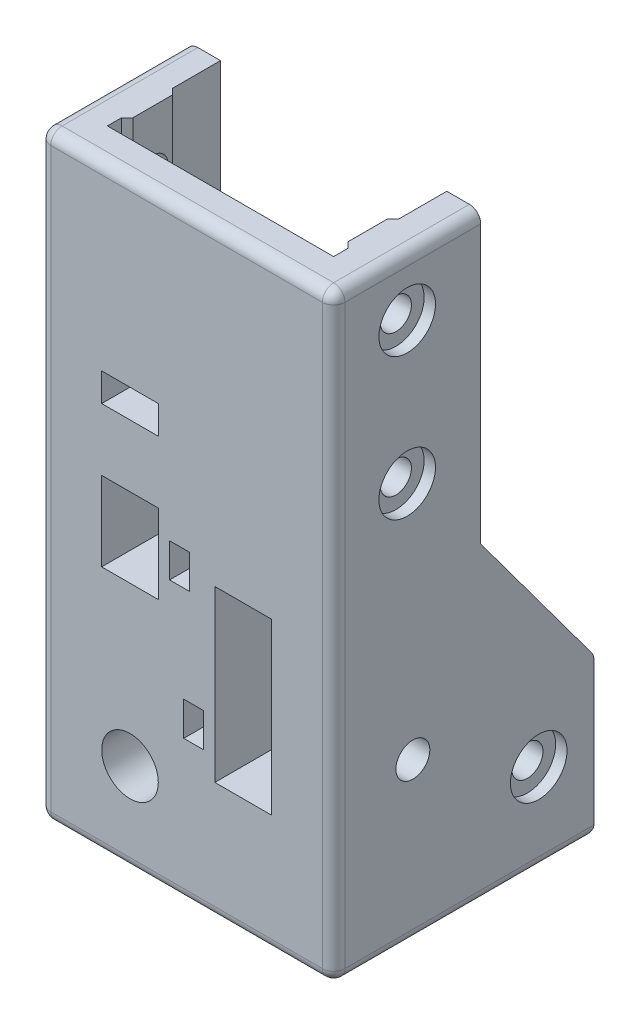
SolidWorks part; units mm, degrees
ref_plane "Front Plane" through (0, 0, 0) normal (0, 0, 1) x (1, 0, 0)
ref_plane "Top Plane" through (0, 0, 0) normal (0, 1, 0) x (1, 0, 0)
ref_plane "Right Plane" through (0, 0, 0) normal (1, 0, 0) x (0, 0, -1)
sketch "Sketch1" plane through (0, 0, 0) normal (1, 0, 0) x (0, 0, -1)
  line L0 (0, 106) -> (26, 106)
  line L1 (0, 0) -> (46, 0)
  line L2 (0, 106) -> (0, 0)
  line L3 (46, 0) -> (46, 55)
  line L4 (26, 106) -> (26, 55)
  line L5 (26, 55) -> (46, 55)
  line L6 (6, 106) -> (6, 58)
  line L7 (46, 6) -> (26, 6)
  line L8 (6, 58) -> (26, 58)
  line L10 (26, 55) -> (26, 6)
  circle A0 centre (13, 95.75) radius 2.75
  circle A1 centre (13, 95.75) radius 5
  circle A2 centre (13, 70.75) radius 2.75
  circle A3 centre (13, 70.75) radius 5
  circle A4 centre (36.25, 15.75) radius 2.75
  circle A5 centre (36.25, 15.75) radius 5
  point P9 (13, 106)
  point P15 (8.8717, 6)
  point P19 (26, 58)
  point P20 (35.1327, 30.1857)
  point P21 (26, 6)
  point P26 (35.8678, 13.2319)
  dimension "D6" = 2.75
  dimension "D7" = 5
  dimension "D1" = 46
  dimension "D2" = 26
  dimension "D3" = 106
  dimension "D4" = 55
  dimension "D5" = 10.25
  dimension "D8" = 25
  dimension "D9" = 6
  dimension "D10" = 6
  dimension "D11" = 58
  dimension "D12" = 15.75
  dimension "D13" = 9.75
extrude "Boss-Extrude1" add sketch "Sketch1" along normal mid plane 52 contours L10 L4 L8 L6 L0 L2 L1 L3 L7 | L5 L10 L7 L3 | A3 A2 | A1 A0 | L6 L8 L4 L0 A3 A1 | A5 A4 region at (0, 35.3382, -12.9374) region at (0, 81.7555, -16.5869) region at (0, 31.7851, -35.9782) region at (0, 95.75, -8.1414) region at (0, 70.75, -8.1414) region at (0, 15.75, -31.3914)
chamfer "Chamfer1" distance 27 distance2 20 1 edges at (0, 55, -46) first distance on face at (0, 27.5, -46)
extrude "Cut-Extrude1" cut sketch "Sketch1<3>" against normal mid plane 40 contours L5 L10 L7 L3 | L6 L8 L4 L0 A3 A1 | A3 A2 | A1 A0 | A5 A4 region at (0, 81.7555, -16.5869) region at (0, 31.7851, -35.9782) region at (0, 95.75, -8.1414) region at (0, 70.75, -8.1414) region at (0, 15.75, -31.3914)
sketch "Sketch1<3>" plane through (0, 0, 0) normal (1, 0, 0) x (0, 0, -1) same geometry as "Sketch1"
sketch "Sketch2" plane through (0, 0, -26) normal (0, 0, -1) x (-1, 0, 0)
  line L0 (20, 58) -> (-20, 58) construction
  line L1 (-20, 58) -> (-5, 58)
  line L2 (-20, 58) -> (-20, 46)
  line L3 (-20, 46) -> (-5, 46)
  line L4 (-5, 58) -> (-5, 46)
  line L5 (5, 58) -> (15, 58)
  line L6 (5, 58) -> (5, 44)
  line L7 (5, 44) -> (15, 44)
  line L8 (15, 58) -> (15, 44)
  dimension "D1" = 15
  dimension "D2" = 12
  dimension "D3" = 10
  dimension "D4" = 14
  dimension "D5" = 10
extrude "Cut-Extrude2" cut sketch "Sketch2" against normal up to surface (20 mm away) up to face at (0, 82, -6)
sketch "Sketch3" plane through (0, 0, 0) normal (0, 0, 1) x (1, 0, 0)
  line L0 (5, 51) -> (15, 51)
  line L1 (-15, 74) -> (-5, 74)
  line L2 (-15, 74) -> (-15, 44)
  line L3 (-15, 44) -> (-5, 44)
  line L4 (-5, 74) -> (-5, 44)
  line L5 (5, 51) -> (5, 21)
  line L6 (-5, 44) -> (-15, 44) construction
  line L7 (-15, 44) -> (-15, 58) construction
  line L8 (-15, 69) -> (-5, 69)
  line L9 (-15, 58) -> (-5, 58)
  line L10 (-20, 58) -> (-15, 58) construction
  line L11 (5, 21) -> (15, 21)
  line L12 (15, 51) -> (15, 21)
  line L13 (5, 46) -> (15, 46)
  line L14 (5, 35) -> (15, 35)
  line L15 (20, 46) -> (5, 46) construction
  line L16 (5, 46) -> (5, 58) construction
  line L17 (10, 21) -> (10, 35) construction
  line L18 (-10, 44) -> (-10, 58) construction
  line L19 (0.5, 48) -> (-3, 48)
  line L20 (3, 25) -> (-0.5, 25)
  line L21 (3, 25) -> (3, 31)
  line L22 (3, 31) -> (-0.5, 31)
  line L23 (-0.5, 25) -> (-0.5, 31)
  line L24 (3, 25) -> (-0.5, 31) construction
  line L25 (3, 31) -> (-0.5, 25) construction
  line L26 (0.5, 48) -> (0.5, 54)
  line L27 (0.5, 54) -> (-3, 54)
  line L28 (-3, 48) -> (-3, 54)
  line L29 (0.5, 48) -> (-3, 54) construction
  line L30 (0.5, 54) -> (-3, 48) construction
  circle A0 centre (-10, 16) radius 5
  circle A1 centre (-10, 16) radius 2.75
  point P23 (-10, 44)
  point P34 (1.25, 28)
  point P39 (0, 0)
  point P40 (10, 28)
  point P41 (-2.506, 28)
  point P42 (-1.25, 51)
  point P47 (-10, 51)
  dimension "D9" = 5
  dimension "D10" = 2.75
  dimension "D1" = 11
  dimension "D2" = 10
  dimension "D3" = 10
  dimension "D4" = 5
  dimension "D5" = 5
  dimension "D6" = 11
  dimension "D7" = 14
  dimension "D8" = 28
  dimension "D11" = 3.5
  dimension "D12" = 6
  dimension "D13" = 2
  dimension "D14" = 3.5
  dimension "D15" = 6
  dimension "D16" = 2
extrude "Cut-Extrude3" cut sketch "Sketch3" against normal through all contours A1 | L5 L13 L12 L0 | L14 L5 L11 L12 | L9 L2 L3 L4 | L2 L8 L4 L1 region at (10, 48.5, 0) region at (10, 28, 0) region at (-10, 71.5, 0) region at (-10, 51, 0) region at (-10, 16, 0)
extrude "Cut-Extrude4" cut sketch "Sketch3<3>" against normal blind 22 contours A0 A1 | L23 L20 L21 L22 | L28 L19 L26 L27 region at (-1.25, 51, 0) region at (1.25, 28, 0) region at (-14.8586, 16, 0)
sketch "Sketch3<3>" plane through (0, 0, 0) normal (0, 0, 1) x (1, 0, 0) same geometry as "Sketch3"
extrude "Cut-Extrude5" cut sketch "Sketch3<4>" against normal blind 11 contours L5 L14 L12 L13 region at (10, 40.5, 0)
sketch "Sketch3<4>" plane through (0, 0, 0) normal (0, 0, 1) x (1, 0, 0) same geometry as "Sketch3"
sketch "Sketch4" plane through (0, 0, 0) normal (1, 0, 0) x (0, 0, -1)
  line L0 (26, 21) -> (26, 35) construction
  line L2 (26, 44) -> (26, 58) construction
  line L3 (0, 106) -> (0, 0) construction
  circle A0 centre (14, 28) radius 1.5
  circle A1 centre (14, 28) radius 3
  circle A2 centre (14, 51) radius 1.5
  circle A3 centre (14, 51) radius 3
  point P3 (10.9426, 24.6286)
  point P6 (0, 0)
  point P7 (26, 28)
  point P8 (0, 0)
  point P15 (12.7722, 46.8378)
  point P16 (0, 0)
  point P17 (0, 0)
  point P20 (26, 51)
  point P21 (0, 0)
  point P22 (19.6179, 28)
  dimension "D1" = 6
  dimension "D2" = 3
  dimension "D3" = 14
extrude "Cut-Extrude6" cut sketch "Sketch4" against normal up to surface (15 mm away) and the other way through all contours A0 region at (0, 28, -14) up to face at (-15, 52.4, -11.6)
extrude "Cut-Extrude7" cut sketch "Sketch4<3>" against normal through all and the other way up to surface (15 mm away) contours A2 region at (0, 51, -14) other way up to face at (15, 26.5, -14)
sketch "Sketch4<3>" plane through (0, 0, 0) normal (1, 0, 0) x (0, 0, -1) same geometry as "Sketch4"
extrude "Cut-Extrude8" cut sketch "Sketch4<4>" against normal blind 8 from surface contours A1 A0 region at (0, 28, -11.0849) starting at face at (26, 28, -15.5)
sketch "Sketch4<4>" plane through (0, 0, 0) normal (1, 0, 0) x (0, 0, -1) same geometry as "Sketch4"
extrude "Cut-Extrude9" cut sketch "Sketch4<5>" along normal blind 8 from surface contours A3 A2 region at (0, 51, -11.0849) starting at face at (-26, 51, -15.5)
sketch "Sketch4<5>" plane through (0, 0, 0) normal (1, 0, 0) x (0, 0, -1) same geometry as "Sketch4"
extrude "Cut-Extrude10" cut sketch "Sketch1<4>" against normal blind 2 from surface contours A1 A0 | A3 A2 | A5 A4 region at (0, 95.75, -8.1414) region at (0, 70.75, -8.1414) region at (0, 15.75, -31.3914) starting at face at (26, 28, -17)
sketch "Sketch1<4>" plane through (0, 0, 0) normal (1, 0, 0) x (0, 0, -1) same geometry as "Sketch1"
extrude "Cut-Extrude11" cut sketch "Sketch1<5>" along normal blind 2 from surface contours A5 A4 | A3 A2 | A1 A0 region at (0, 95.75, -8.1414) region at (0, 70.75, -8.1414) region at (0, 15.75, -31.3914) starting at face at (-26, 70.75, -15.75)
sketch "Sketch1<5>" plane through (0, 0, 0) normal (1, 0, 0) x (0, 0, -1) same geometry as "Sketch1"
sketch "Sketch5" plane through (0, 0, -46) normal (0, 0, -1) x (-1, 0, 0)
  line L0 (0, 0) -> (0, 106) construction
  line L1 (20, 106) -> (-20, 106) construction
  line L2 (20, 6) -> (-20, 6) construction
  line L3 (-14.25, 6) -> (-5.25, 6)
  line L4 (-14.25, 6) -> (-14.25, 7)
  line L5 (-14.25, 7) -> (-5.25, 7)
  line L6 (-5.25, 6) -> (-5.25, 7)
  line L7 (5.25, 6) -> (5.25, 7)
  line L8 (14.25, 7) -> (5.25, 7)
  line L9 (14.25, 6) -> (14.25, 7)
  line L10 (14.25, 6) -> (5.25, 6)
  line L11 (-20, 46) -> (-20, 6) construction
  line L12 (-20, 20.25) -> (-19, 20.25)
  line L13 (-20, 20.25) -> (-20, 11.25)
  line L14 (-20, 11.25) -> (-19, 11.25)
  line L15 (-19, 20.25) -> (-19, 11.25)
  line L16 (19, 20.25) -> (19, 11.25)
  line L17 (20, 11.25) -> (19, 11.25)
  line L18 (20, 20.25) -> (20, 11.25)
  line L19 (20, 20.25) -> (19, 20.25)
  line L20 (-26, 20.75) -> (-26, 10.75) construction
  line L21 (-26, 20.75) -> (-26, 10.75) construction
  point P29 (-26, 15.75)
  point P30 (-20, 15.75)
  dimension "D1" = 9
  dimension "D2" = 1
  dimension "D3" = 10.5
  dimension "D4" = 9
  dimension "D5" = 1
sketch "Sketch6" plane through (0, 6, 0) normal (0, 1, 0) x (1, 0, 0)
  line L0 (19, 17.5) -> (19, 8.5)
  line L1 (-24, 15.75) -> (-24, 10.25) construction
  line L2 (-14.25, 46) -> (-5.25, 46) construction
  line L3 (-20, 6) -> (-20, 26) construction
  line L4 (-20, 17.5) -> (-19, 17.5)
  line L5 (-20, 17.5) -> (-20, 8.5)
  line L6 (-20, 8.5) -> (-19, 8.5)
  line L7 (-19, 17.5) -> (-19, 8.5)
  line L8 (0, 46) -> (0, 0) construction
  line L9 (-20, 46) -> (20, 46) construction
  line L10 (-24, 15.75) -> (-24, 10.25) construction
  line L11 (20, 8.5) -> (19, 8.5)
  line L12 (20, 17.5) -> (20, 8.5)
  line L13 (20, 17.5) -> (19, 17.5)
  circle A0 centre (-9.75, 36.25) radius 2.75
  circle A1 centre (-9.75, 36.25) radius 5
  circle A2 centre (9.75, 36.25) radius 5
  circle A3 centre (9.75, 36.25) radius 2.75
  point P6 (-9.75, 46)
  point P17 (-19, 31.7229)
  point P18 (-20, 13)
  point P21 (-24, 13)
  dimension "D1" = 5.5
  dimension "D2" = 10
  dimension "D3" = 9.75
  dimension "D4" = 9
  dimension "D5" = 1
extrude "Boss-Extrude2" add sketch "Sketch4<6>" against normal blind 0.5 from surface contours A3 A2 region at (0, 51, -11.0849) starting at face at (-5, 52.5, -14)
sketch "Sketch4<6>" plane through (0, 0, 0) normal (1, 0, 0) x (0, 0, -1) same geometry as "Sketch4"
extrude "Boss-Extrude3" add sketch "Sketch4<7>" along normal blind 0.5 from surface contours A3 A2 region at (0, 51, -11.0849) starting at face at (-15, 49.5, -14)
sketch "Sketch4<7>" plane through (0, 0, 0) normal (1, 0, 0) x (0, 0, -1) same geometry as "Sketch4"
extrude "Boss-Extrude4" add sketch "Sketch4<8>" along normal blind 0.5 from surface contours A1 A0 region at (0, 28, -11.0849) starting at face at (5, 49.5, -14)
sketch "Sketch4<8>" plane through (0, 0, 0) normal (1, 0, 0) x (0, 0, -1) same geometry as "Sketch4"
extrude "Boss-Extrude5" add sketch "Sketch4<9>" against normal blind 0.5 from surface contours A1 A0 region at (0, 28, -11.0849) starting at face at (15, 26.5, -14)
sketch "Sketch4<9>" plane through (0, 0, 0) normal (1, 0, 0) x (0, 0, -1) same geometry as "Sketch4"
extrude "Boss-Extrude6" add sketch "Sketch5" against normal up to surface (20 mm away) up to face at (-10, 18.75, -26)
extrude "Boss-Extrude7" add sketch "Sketch6" against normal up to body from surface separate body contours L12 L13 L0 L11 | L7 L4 L5 L6 region at (19.5, 6, -13) region at (-19.5, 6, -13) starting at face at (0, 106, -14.5)
extrude "Cut-Extrude12" cut sketch "Sketch1<6>" against normal through all both and the other way through all contours A0 | A2 | A4 region at (0, 95.75, -13) region at (0, 70.75, -13) region at (0, 15.75, -36.25)
sketch "Sketch1<6>" plane through (0, 0, 0) normal (1, 0, 0) x (0, 0, -1) same geometry as "Sketch1"
extrude "Cut-Extrude13" cut sketch "Sketch6<3>" against normal through all both and the other way through all contours A0 | A3 region at (-9.75, 6, -36.25) region at (9.75, 6, -36.25)
sketch "Sketch6<3>" plane through (0, 6, 0) normal (0, 1, 0) x (1, 0, 0) same geometry as "Sketch6"
extrude "Cut-Extrude14" cut sketch "Sketch6<4>" along normal blind 2 from surface contours A2 A3 | A1 A0 region at (-14.6086, 6, -36.25) region at (4.8914, 6, -36.25) starting at face at (0, 0, -23)
sketch "Sketch6<4>" plane through (0, 6, 0) normal (0, 1, 0) x (1, 0, 0) same geometry as "Sketch6"
chamfer "Chamfer2" distance 1 12 edges at (-19, 11.25, -36) (-19, 20.25, -36) (-5.25, 7, -36) (-14.25, 7, -36) (5.25, 7, -36) (14.25, 7, -36) (19, 11.25, -36) (19, 20.25, -36) (19, 76, -8.5) (19, 76, -17.5) (-19, 82, -8.5) (-19, 82, -17.5)
chamfer "Chamfer3" distance 0.5 angle 45 4 edges at (5.5, 25, -14) (14.5, 25, -14) (-5.5, 54, -14) (-14.5, 48, -14)
fillet "Fillet1" radius 2 11 edges at (26, 106, -13) (-26, 106, -13) (0, 106, 0) (-26, 53, 0) (-23, 28, -46) (23, 28, -46) (-26, 0, -23) (0, 0, -46) (26, 0, -23) (0, 0, 0) (26, 53, 0)
